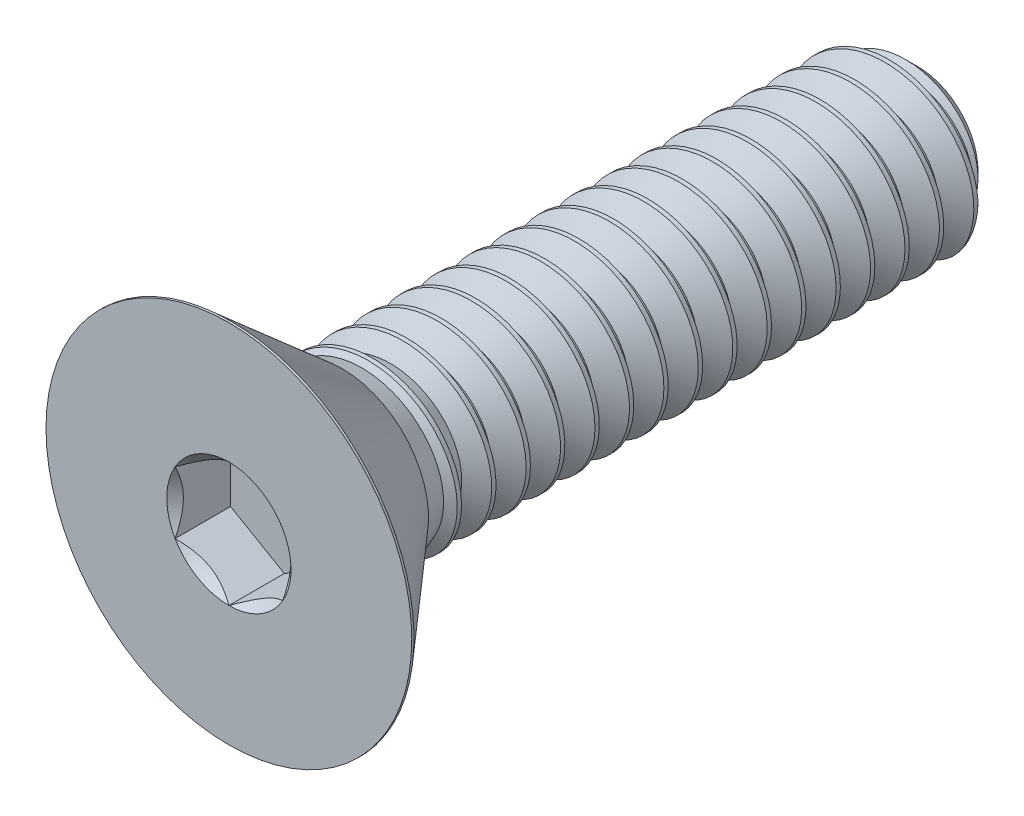
SolidWorks part; units mm, degrees
material "AISI 1020"
ref_plane "Front Plane" through (0, 0, 0) normal (0, 0, 1) x (1, 0, 0)
ref_plane "Top Plane" through (0, 0, 0) normal (0, 1, 0) x (1, 0, 0)
ref_plane "Right Plane" through (0, 0, 0) normal (1, 0, 0) x (0, 0, -1)
sketch "Sketch1" plane through (0, 0, 0) normal (1, 0, 0) x (0, 0, -1)
  line L0 (-12.7, 0) -> (12.7, 0) construction
  line L1 (-12.7, 0) -> (-12.7, 6.7437)
  line L2 (-12.7, 6.7437) -> (-12.6182, 6.7437)
  line L3 (-12.6182, 6.7437) -> (-8.6106, 3.2599)
  line L4 (-12.6182, -6.7437) -> (-8.6106, -3.2599)
  line L5 (12.7, 0) -> (12.7, 3.175)
  line L6 (12.7, 3.175) -> (-8.6106, 3.175)
  line L7 (11.7475, 3.175) -> (12.7, 2.2225)
  line L8 (12.6206, 3.3125) -> (13.2556, 2.2126) construction
  line L9 (13.2556, 2.2126) -> (13.8906, 3.3125) construction
  line L10 (13.8906, 3.3125) -> (12.6206, 3.3125) construction
  line L11 (12.6603, 3.2437) -> (13.8509, 3.2437)
  line L12 (13.8509, 3.2437) -> (13.335, 2.3501)
  line L13 (13.335, 2.3501) -> (13.1762, 2.3501)
  line L14 (13.1762, 2.3501) -> (12.6603, 3.2437)
  line L15 (13.2556, 2.3501) -> (13.2556, 2.2126) construction
  line L16 (12.7, 3.175) -> (13.8112, 3.175) construction
  line L17 (13.2556, 3.3125) -> (13.2556, 3.175) construction
  line L18 (12.7, -3.175) -> (-8.6106, -3.175)
  arc A0 (-8.6106, 3.2599) -> (-8.3834, 3.175) centre (-8.3834, 3.5213) ccw
  point P2 (0, 0)
  point P23 (-10.6553, 0)
  point P27 (13.2556, 3.2437)
  point P30 (10.795, -3.175)
  point P31 (-8.6106, 6.7437)
  point P33 (-8.6106, -6.7437)
  point P34 (-12.6182, -6.7437)
  dimension "Length" = 25.4
  dimension "Head Height" = 4.0894
  dimension "Head Diameter" = 13.4874
  dimension "Countersink Angle" = 82
  dimension "Screw Size Decimal Equivalent" = 6.35
  dimension "Pitch" = 1.27
  dimension "D4" = 0.1588
  dimension "D3" = 45
  dimension "D5" = 0.9525
  dimension "D6" = 2.0447
  dimension "D1" = 1.905
  dimension "D7" = 0.0818
sketch "Sketch8" plane through (0, 0, 0) normal (0, 0, 1) x (1, 0, 0)
  line L1 (0, 2.2914) -> (-1.9844, 1.1457)
  line L2 (-1.9844, 1.1457) -> (-1.9844, -1.1457)
  line L3 (-1.9844, -1.1457) -> (0, -2.2914)
  line L4 (0, -2.2914) -> (1.9844, -1.1457)
  line L5 (1.9844, -1.1457) -> (1.9844, 1.1457)
  line L6 (1.9844, 1.1457) -> (0, 2.2914)
  circle A0 centre (0, 0) radius 1.9844 construction
  dimension "Drive Size" = 3.9688
sketch "Sketch2" plane through (0, 0, 0) normal (1, 0, 0) x (0, 0, -1)
  line L0 (-12.6182, 6.7437) -> (-8.6106, 3.2599) construction
  line L1 (-12.7, 0) -> (-12.7, 6.7437) construction
  line L2 (-12.6182, 6.7437) -> (-8.5129, 3.175)
  line L3 (-12.7, 0) -> (-12.7, 6.7437)
  line L4 (-12.7, 6.7437) -> (-12.6182, 6.7437) construction
  line L5 (-12.7, 6.7437) -> (-12.6182, 6.7437)
  line L6 (-8.5129, 3.175) -> (11.7475, 3.175)
  line L7 (11.7475, 3.175) -> (12.7, 2.2225)
  line L8 (12.7, 2.2225) -> (12.7, 0)
  line L9 (12.7, 0) -> (-12.7, 0)
revolve "Revolve1" add sketch "Sketch2" angle 360 about L9
sketch "Sketch9" plane through (0, 0, 12.7) normal (0, 0, 1) x (1, 0, 0)
  line L0 (1.9844, -1.1457) -> (1.9844, 1.1457) construction
  line L1 (0, -2.2914) -> (1.9844, -1.1457) construction
  line L2 (-1.9844, -1.1457) -> (0, -2.2914) construction
  line L3 (-1.9844, 1.1457) -> (-1.9844, -1.1457) construction
  line L4 (0, 2.2914) -> (-1.9844, 1.1457) construction
  line L5 (1.9844, 1.1457) -> (0, 2.2914) construction
  line L6 (1.9844, -1.1457) -> (1.9844, 1.1457)
  line L7 (0, -2.2914) -> (1.9844, -1.1457)
  line L8 (-1.9844, -1.1457) -> (0, -2.2914)
  line L9 (-1.9844, 1.1457) -> (-1.9844, -1.1457)
  line L10 (0, 2.2914) -> (-1.9844, 1.1457)
  line L11 (1.9844, 1.1457) -> (0, 2.2914)
sketch "Sketch10" plane through (0, 0, 12.7) normal (0, 0, 1) x (1, 0, 0)
  circle A0 centre (0, 0) radius 2.2914
extrude "Cut-Extrude2" cut sketch "Sketch10" against normal up to vertex (2.0447 mm away) draft 45 up to point (0, 0, 10.6553)
extrude "Cut-Extrude1" cut sketch "Sketch9" against normal up to vertex (2.0447 mm away) up to point (0, 0, 10.6553)
ref_plane "Plane1" through (0, 0, 8.5129) normal (0, 0, 1) x (1, 0, 0)
split "Split1" trim tools "Plane1" bodies to split 111 resulting bodies 105 106
sketch "Sketch3" plane through (0, 0, -12.7) normal (0, 0, -1) x (-1, 0, 0)
  circle A0 centre (0, 0) radius 3.175 construction
  circle A1 centre (0, 0) radius 3.175
curve "Helix/Spiral1" pitch 1.27 height 25.4 radius 3.175 centre (0, 0, -12.7) axis (0, 0, 1) start towards (0, 1, 0)
sketch "Sketch4" plane through (0, 0, 0) normal (1, 0, 0) x (0, 0, -1)
  line L0 (12.6603, 3.2437) -> (13.8509, 3.2437) construction
  line L1 (13.1762, 2.3501) -> (12.6603, 3.2437) construction
  line L2 (13.335, 2.3501) -> (13.1762, 2.3501) construction
  line L3 (13.8509, 3.2437) -> (13.335, 2.3501) construction
  line L4 (12.6603, 3.2437) -> (13.8509, 3.2437)
  line L5 (13.1762, 2.3501) -> (12.6603, 3.2437)
  line L6 (13.335, 2.3501) -> (13.1762, 2.3501)
  line L7 (13.8509, 3.2437) -> (13.335, 2.3501)
sweep "Cut-Sweep1" cut profiles "Sketch4" path "Helix/Spiral1" align with end faces yes
sketch "Sketch7" plane through (0, 0, 8.5129) normal (0, 0, 1) x (1, 0, 0)
  circle A0 centre (0, 0) radius 3.175
extrude "Boss-Extrude2" add sketch "Sketch7" against normal up to next (21.2129 mm away) draft 20
equation "\"D4@Sketch1\" = \"Pitch@Sketch1\" / 8"
equation "\"D5@Sketch1\"=\"Pitch@Sketch1\"*0.75"
equation "\"D4@Helix/Spiral1\"=\"Pitch@Sketch1\""
equation "\"D3@Helix/Spiral1\"=\"Length@Sketch1\""
equation "\"D6@Sketch1\"=\"Head Height@Sketch1\"/2"
equation "\"D1@Sketch1\"=\"Pitch@Sketch1\"*1.5"
equation "\"D7@Sketch1\"=\"Head Height@Sketch1\"*0.02"
